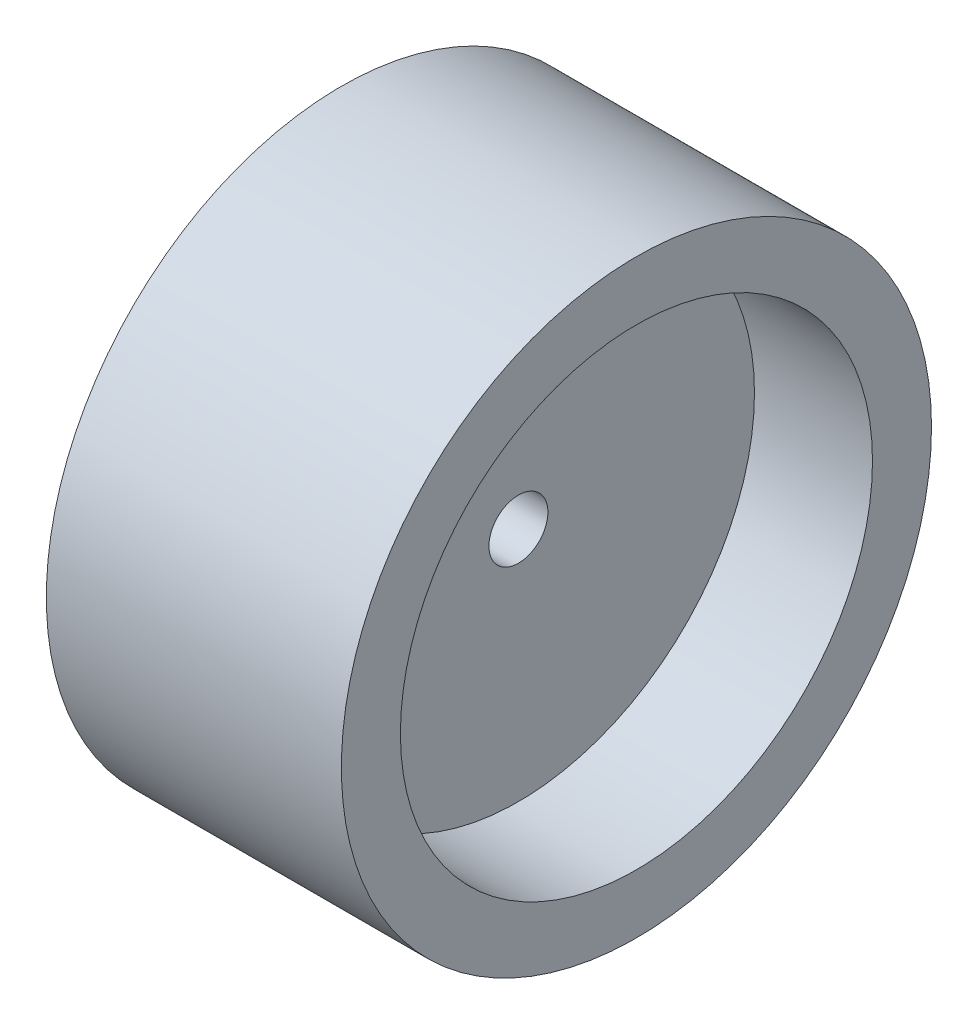
SolidWorks part; units mm, degrees
ref_plane "Front Plane" through (0, 0, 0) normal (0, 0, 1) x (1, 0, 0)
ref_plane "Top Plane" through (0, 0, 0) normal (0, 1, 0) x (1, 0, 0)
ref_plane "Right Plane" through (0, 0, 0) normal (1, 0, 0) x (0, 0, -1)
sketch "Sketch1" plane through (0, 0, 0) normal (1, 0, 0) x (0, 0, -1)
  circle A0 centre (0, 0) radius 50
  circle A1 centre (0, 0) radius 5
  dimension "D1" = 100
  dimension "D2" = 10
extrude "Boss-Extrude1" add sketch "Sketch1" along normal mid plane 50
sketch "Sketch3" plane through (0, 0, 0) normal (1, 0, 0) x (0, 0, -1)
  circle A0 centre (0, 0) radius 40
  dimension "D1" = 80
extrude "Cut-Extrude1" cut sketch "Sketch3" against normal blind 20 from offset 5 offset against normal yes
extrude "Cut-Extrude2" cut sketch "Sketch3<2>" along normal blind 20 from offset 5
sketch "Sketch3<2>" plane through (0, 0, 0) normal (1, 0, 0) x (0, 0, -1) same geometry as "Sketch3"
